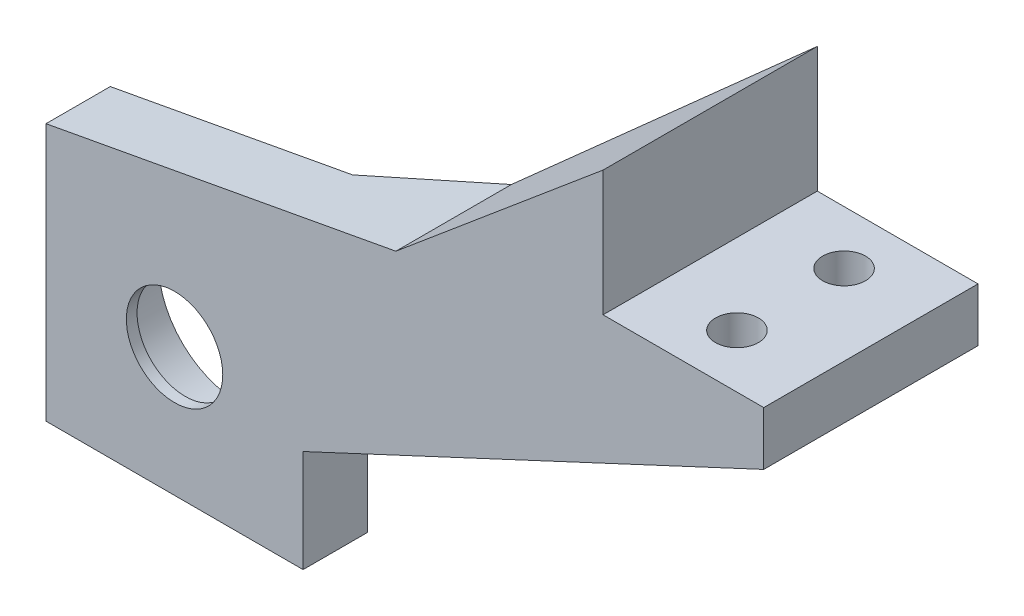
SolidWorks part; units mm, degrees
material "ABS"
ref_plane "Front Plane" through (0, 0, 0) normal (0, 0, 1) x (1, 0, 0)
ref_plane "Top Plane" through (0, 0, 0) normal (0, 1, 0) x (1, 0, 0)
ref_plane "Right Plane" through (0, 0, 0) normal (1, 0, 0) x (0, 0, -1)
sketch "Sketch1" plane through (0, 0, 0) normal (0, 0, 1) x (1, 0, 0)
  circle A0 centre (0, 0) radius 7.5
  circle A1 centre (0, 0) radius 4.5
  circle A2 centre (0, 0) radius 10
  dimension "D1" = 15
  dimension "D2" = 20
  dimension "D3" = 9
extrude "Boss-Extrude1" add sketch "Sketch1" against normal up to surface (5 mm away) contours A2 A0 region at (-9.7172, 0, 0)
extrude "Boss-Extrude2" add sketch "Sketch1<3>" along normal blind 1 contours A0 A1 | A2 A0 region at (-7.2879, 0, 0) region at (-9.7172, 0, 0)
sketch "Sketch1<3>" plane through (0, 0, 0) normal (0, 0, 1) x (1, 0, 0) same geometry as "Sketch1"
sketch "Sketch2" plane through (0, 0, 1) normal (0, 0, 1) x (1, 0, 0)
  line L3 (55, 22.6) -> (40, 22.6)
  line L5 (-12, -0.9326) -> (-12, -12)
  line L6 (-12, -12) -> (12, -12)
  line L8 (40, 22.6) -> (40, 17.6)
  line L13 (40, 17.6) -> (55, 17.6)
  line L14 (55, 17.6) -> (55, 22.6)
  line L15 (-86, 22.6) -> (266, 22.6) construction
  line L16 (10.6203, 22.6) -> (-12, 12.052)
  line L17 (-12, -0.9326) -> (-12, 12.052)
  line L18 (40, 22.6) -> (10.6203, 22.6)
  line L19 (55, 17.6) -> (12, -2.4512)
  line L20 (12, -2.4512) -> (12, -12)
  line L21 (10.6203, 22.6) -> (40, 36.3)
  line L23 (34.0705, 37.9485) -> (-8.8692, 17.9254) construction
  line L24 (40, 22.6) -> (40, 34.3) construction
  line L25 (40, 36.3) -> (40, 22.6)
  circle A1 centre (0, 0) radius 10
  circle A2 centre (0, 0) radius 10 construction
  circle M4 centre (0, 0) radius 10
  dimension "D1" = 12
  dimension "D2" = 24
  dimension "D3" = 15
  dimension "D4" = 5
  dimension "D5" = 25
  dimension "D6" = 4
  dimension "D7" = 12
  dimension "D8" = 2
  dimension "D9" = 0
extrude "Boss-Extrude3" add sketch "Sketch2" against normal up to surface (6 mm away) contours L8 M4 | L6 L5 M4 | L8 | L25 L21 L18 region at (47.5, 20.1, 1) region at (16.0369, 9.9628, 1) region at (30.2068, 27.1667, 1) up to face at (-10, 0, -5)
sketch "Sketch3" plane through (0, 22.6, 0) normal (0, -1, 0) x (1, 0, 0)
  line L0 (40, -286) -> (40, 14) construction
  line L1 (55, -5) -> (40, -5)
  line L2 (55, -5) -> (55, -19)
  line L3 (55, -19) -> (40, -19)
  line L4 (40, -5) -> (40, -19)
  line L5 (55, -5) -> (40, -19) construction
  line L6 (55, -19) -> (40, -5) construction
  line L7 (55, 1) -> (12, 1) construction
  line L8 (40, -19) -> (10.6203, -5)
  line L9 (55, -5) -> (55, 1) construction
  line L10 (40, -5) -> (10.6203, -5)
  line L11 (40, -5) -> (-12, -5) construction
  point P4 (47.5, -12)
  dimension "D1" = 20
  dimension "D2" = 29.3797
extrude "Boss-Extrude7" add sketch "Sketch3" along normal up to surface (11.9946 mm away) contours L4 L10 L8 | L1 L4 L3 L2 region at (47.5, 22.6, -12) region at (30.2068, 22.6, -9.6667) up to face at (33.5, 7.5744, -2)
sketch "Sketch4" plane through (0, 22.6, 0) normal (0, -1, 0) x (1, 0, 0)
  line L1 (55, 1) -> (40, 1)
  line L2 (55, 1) -> (55, -19)
  line L3 (55, -19) -> (40, -19)
  line L4 (40, 1) -> (40, -19)
  line L5 (55, 1) -> (40, -19) construction
  line L6 (55, -19) -> (40, 1) construction
  line L7 (55, -19) -> (55, 1) construction
  line L8 (55, -9) -> (40, -9) construction
  line L9 (47.5, -9.8431) -> (43.9, -11.9215)
  line L10 (43.9, -11.9215) -> (43.9, -16.0785)
  line L11 (43.9, -16.0785) -> (47.5, -18.1569)
  line L12 (47.5, -18.1569) -> (51.1, -16.0785)
  line L13 (51.1, -16.0785) -> (51.1, -11.9215)
  line L14 (51.1, -11.9215) -> (47.5, -9.8431)
  line L21 (51.1, -6.0785) -> (47.5, -8.1569)
  line L22 (51.1, -1.9215) -> (51.1, -6.0785)
  line L23 (47.5, 0.1569) -> (51.1, -1.9215)
  line L24 (43.9, -1.9215) -> (47.5, 0.1569)
  line L25 (43.9, -6.0785) -> (43.9, -1.9215)
  line L26 (47.5, -8.1569) -> (43.9, -6.0785)
  line L27 (55, 1) -> (40, 1) construction
  circle A0 centre (47.5, -14) radius 3.6 construction
  circle A1 centre (47.5, -4) radius 3.6 construction
  circle A2 centre (47.5, -14) radius 2
  circle A3 centre (47.5, -4) radius 2
  point P4 (47.5, -9)
  point P28 (45.7, -10.8823)
  dimension "D3" = 4
  dimension "D1" = 7.5
  dimension "D2" = 7.2
  dimension "D4" = 5
  dimension "D5" = 15
  dimension "D6" = 20
extrude "Cut-Extrude4" cut sketch "Sketch4" along normal through all contours A2 | A3 region at (47.5, 22.6, -14) region at (47.5, 22.6, -4)
extrude "Cut-Extrude5" cut sketch "Sketch4<3>" along normal through all from offset 3 contours L26 L21 L22 L23 L24 L25 A3 | L13 L14 L9 L10 L11 L12 A2 region at (49.245, 22.6, -10.9776) region at (49.245, 22.6, -7.0224)
sketch "Sketch4<3>" plane through (0, 22.6, 0) normal (0, -1, 0) x (1, 0, 0) same geometry as "Sketch4"
extrude "Boss-Extrude8" add sketch "Sketch3<4>" against normal up to surface (13.7 mm away) contours L4 L10 L8 region at (30.2068, 22.6, -9.6667) up to face at (13.3241, 23.8608, -2.6)
sketch "Sketch3<4>" plane through (0, 22.6, 0) normal (0, -1, 0) x (1, 0, 0) same geometry as "Sketch3"
sketch "Sketch6" plane through (0, 0, 1) normal (0, 0, 1) x (1, 0, 0)
  line L0 (20.6588, 18.0708) -> (40, 34.3)
  line L1 (20.6588, 18.0708) -> (56.616, 48.2425) construction
  line L2 (40, 36.3) -> (40, 22.6) construction
  line L3 (20.6588, 18.0708) -> (15.104, 24.6908)
  line L4 (40, 36.3) -> (-12, 12.052) construction
  line L5 (18.5376, 20.5988) -> (20.6588, 18.0708) construction
  line L6 (-12, 12.052) -> (20.6588, 18.0708)
  line L7 (-12, 12.052) -> (40, 36.3)
  line L8 (40, 36.3) -> (40, 34.3)
  line M7 (40, 22.6) -> (40, 36.3)
  line M8 (40, 36.3) -> (-12, 12.052)
extrude "Cut-Extrude6" cut sketch "Sketch6" against normal through all contours L6 L3 M8 | L3 L0 M7 M8 region at (26.4522, 26.8162, 1) region at (7.9209, 18.2712, 1)
